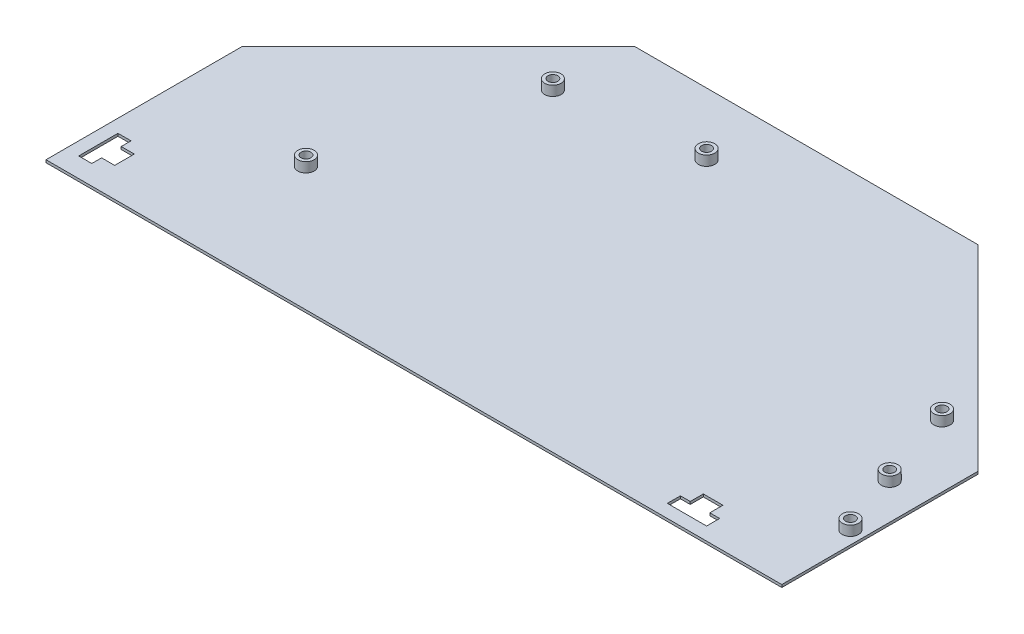
SolidWorks part; units mm, degrees
ref_plane "Front Plane" through (0, 0, 0) normal (0, 0, 1) x (1, 0, 0)
ref_plane "Top Plane" through (0, 0, 0) normal (0, 1, 0) x (1, 0, 0)
ref_plane "Right Plane" through (0, 0, 0) normal (1, 0, 0) x (0, 0, -1)
sketch "Sketch2" plane through (0, 0, 0) normal (0, 1, 0) x (1, 0, 0)
  circle A0 centre (41.5, 38) radius 2.5
  circle A1 centre (59, 96) radius 2.5
  circle A2 centre (101, 101) radius 2.5
  circle A3 centre (206, 68) radius 2.5
  circle A4 centre (214, 44) radius 2.5
  circle A5 centre (221, 25) radius 2.5
extrude "Boss-Extrude1" add sketch "Sketch2" along normal blind 3 contours A2 | A3 | A4 | A5 | A0 | A1 region at (41.5, 0, -38) region at (101, 0, -101) region at (206, 0, -68) region at (214, 0, -44) region at (221, 0, -25)
sketch "Sketch4" plane through (0, 0, 0) normal (0, 1, 0) x (1, 0, 0)
  line L1 (0, 0) -> (225, 0)
  line L2 (0, 0) -> (0, 120)
  line L3 (0, 120) -> (225, 120)
  line L4 (225, 0) -> (225, 120)
  circle A2 centre (221, 25) radius 2.5 construction
  dimension "D1" = 120
  dimension "D2" = 4
  dimension "D3" = 225
extrude "Boss-Extrude2" add sketch "Sketch4" against normal blind 0.8
sketch "Sketch9" plane through (0, 3, 0) normal (0, 1, 0) x (1, 0, 0)
  point P0 (59, 96)
  point P3 (101, 101)
  point P6 (206, 68)
  point P9 (214, 44)
  point P12 (221, 25)
  point P15 (41.5, 38)
sketch "Sketch14" plane through (0, 3, 0) normal (0, 1, 0) x (1, 0, 0)
  point P0 (59, 96)
  point P4 (101, 101)
  point P7 (206, 68)
  point P10 (214, 44)
  point P13 (221, 25)
  point P16 (41.5, 38)
sketch "Sketch17" plane through (0, 3, 0) normal (0, 1, 0) x (1, 0, 0)
  point P0 (59, 96)
sketch "Sketch22" plane through (0, 3, 0) normal (0, 1, 0) x (1, 0, 0)
  point P0 (59, 96)
  point P3 (101, 101)
  point P6 (206, 68)
  point P9 (214, 44)
  point P12 (221, 25)
  point P15 (41.5, 38)
hole_wizard "Ø3.0mm Dowel Hole1" positions "Sketch22" profile "Sketch21" hole size "Ø3.0" standard "ANSI Metric"
sketch "Sketch21" plane through (59, 3, -96) normal (1, 0, 0) x (0, 0, 1)
  line L0 (0, 0) -> (0, 4)
  line L1 (0, 4) -> (1.5, 4)
  line L2 (1.5, 4) -> (1.5, 0)
  line L5 (1.5, 0) -> (0, 0)
  line L10 (0, 4) -> (-1.5, 4) construction
  line L11 (0, -6.35) -> (0, 107.95) construction
  dimension "Hole Dia." = 3
  dimension "Hole Depth" = 4
  dimension "Drill Angle" = 180
sketch "Sketch27" plane through (0, 0, 0) normal (0, 1, 0) x (1, 0, 0)
  line L1 (186, 8) -> (189, 8)
  line L2 (186, 8) -> (186, 4)
  line L3 (186, 4) -> (198, 4)
  line L4 (198, 8) -> (198, 4)
  line L5 (0, 0) -> (225, 0) construction
  line L6 (225, 0) -> (225, 120) construction
  line L9 (195, 8) -> (198, 8)
  line L11 (189, 8) -> (189, 12)
  line L12 (189, 12) -> (195, 12)
  line L13 (195, 8) -> (195, 12)
  line L14 (0, 120) -> (0, 0) construction
  line L15 (4, 6) -> (8, 6)
  line L16 (4, 6) -> (4, 18)
  line L17 (4, 18) -> (8, 18)
  line L18 (8, 6) -> (8, 9)
  line L19 (8, 15) -> (8, 18)
  line L20 (8, 15) -> (12, 15)
  line L22 (8, 9) -> (12, 9)
  line L23 (12, 15) -> (12, 9)
  dimension "D1" = 4
  dimension "D2" = 27
  dimension "D3" = 12
  dimension "D4" = 4
  dimension "D5" = 4
  dimension "D6" = 3
  dimension "D7" = 3
  dimension "D8" = 6
  dimension "D9" = 4
  dimension "D10" = 12
  dimension "D11" = 4
  dimension "D12" = 4
  dimension "D13" = 3
  dimension "D14" = 3
extrude "Cut-Extrude1" cut sketch "Sketch27" against normal up to next
chamfer "Chamfer1" distance 60 angle 45 2 edges at (0, -0.4, -120) (225, -0.4, -120)
